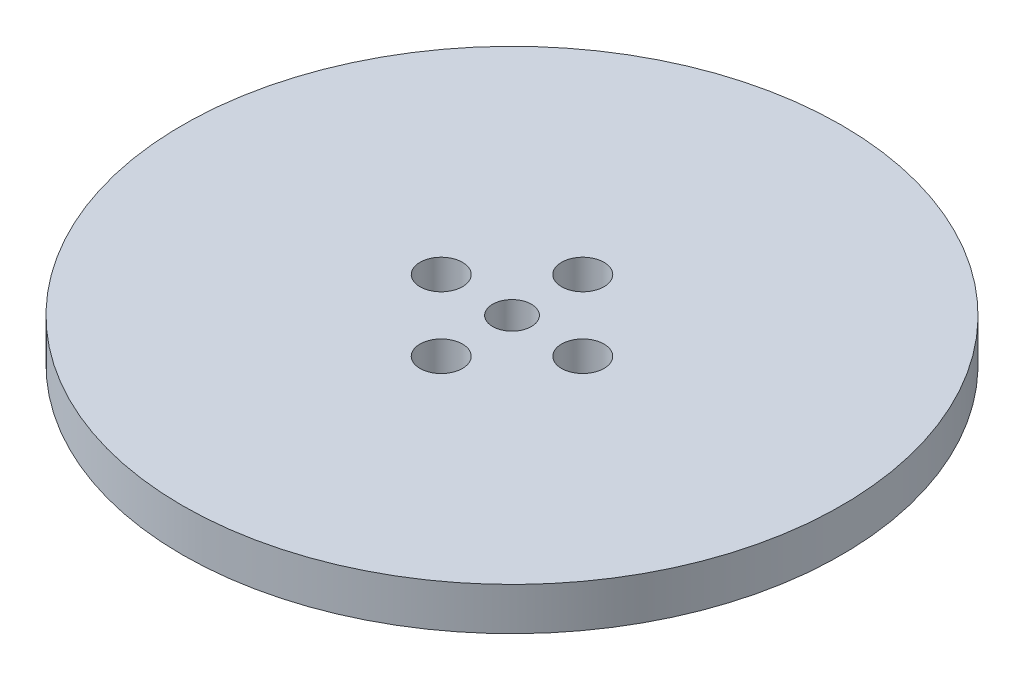
SolidWorks part; units mm, degrees
ref_plane "Front Plane" through (0, 0, 0) normal (0, 0, 1) x (1, 0, 0)
ref_plane "Top Plane" through (0, 0, 0) normal (0, 1, 0) x (1, 0, 0)
ref_plane "Right Plane" through (0, 0, 0) normal (1, 0, 0) x (0, 0, -1)
sketch "Sketch1" plane through (0, 0, 0) normal (0, 1, 0) x (1, 0, 0)
  circle A0 centre (0, 0) radius 85
  dimension "FLANGE_OD" = 170
extrude "Boss-Extrude1" add sketch "Sketch1" along normal blind 11
sketch "Sketch2" plane through (0, 0, 0) normal (0, 1, 0) x (1, 0, 0)
  circle A0 centre (0, 0) radius 5
  dimension "BORE_D" = 10
extrude "Cut-Extrude1" cut sketch "Sketch2" along normal through all
sketch "Sketch3" plane through (0, 11, 0) normal (0, 1, 0) x (1, 0, 0)
  circle A0 centre (0, 0) radius 18.2555 construction
  circle A1 centre (-18.2555, 0) radius 5.4727
  dimension "BOLT_D" = 10.9453
  dimension "BOLT_PCD" = 36.5111
extrude "Cut-Extrude2" cut sketch "Sketch3" against normal blind 8.4618
pattern_circular "CirPattern1" count 4 over 360 about axis through (0, 0, 0) along (0, 1, 0) of "Cut-Extrude2"
